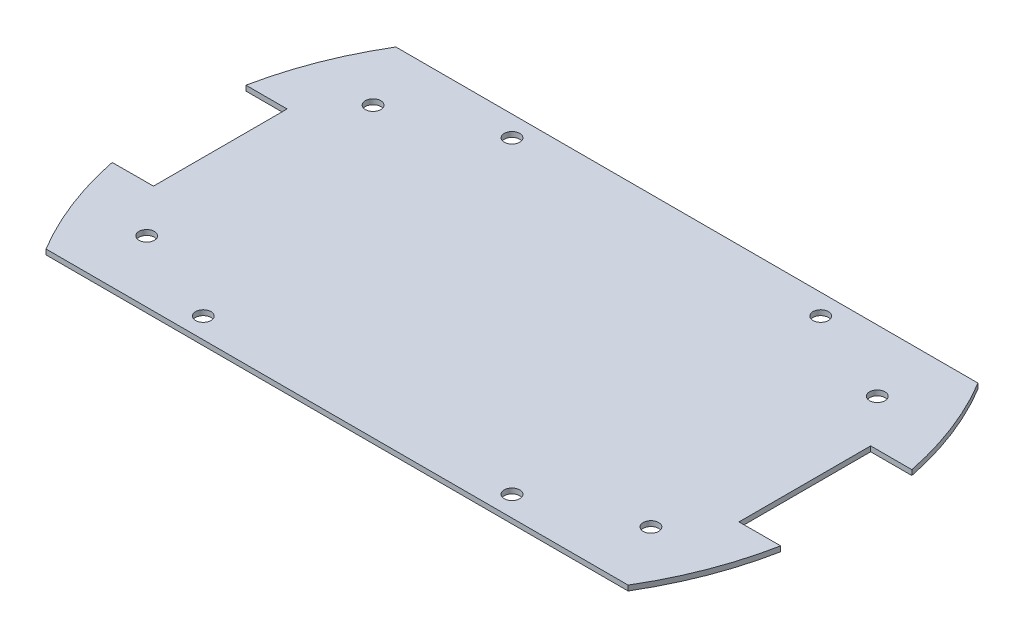
SolidWorks part; units mm, degrees
ref_plane "前基準面" through (0, 0, 0) normal (0, 0, 1) x (1, 0, 0)
ref_plane "上基準面" through (0, 0, 0) normal (0, 1, 0) x (1, 0, 0)
ref_plane "右基準面" through (0, 0, 0) normal (1, 0, 0) x (0, 0, -1)
sketch "草圖7" plane through (0, 0, 0) normal (0, 1, 0) x (1, 0, 0)
  line L1 (-34, 34) -> (34, 34)
  line L2 (-34, 34) -> (-34, -34)
  line L3 (-34, -34) -> (34, -34)
  line L4 (34, 34) -> (34, -34)
  line L5 (-34, 34) -> (34, -34) construction
  line L6 (-34, -34) -> (34, 34) construction
  point P0 (0, 0)
  point P7 (-30, 30)
  point P10 (30, 30)
  point P11 (30, -30)
  point P12 (-30, -30)
  point P13 (0, 0)
  dimension "D1" = 68
  dimension "D2" = 4
  dimension "D3" = 4
sketch "草圖10" plane through (0, 0, 0) normal (0, 1, 0) x (1, 0, 0)
  line L0 (-56.5685, 34) -> (56.5685, 34)
  line L1 (-34, 34) -> (34, 34) construction
  line L2 (-56.5685, -34) -> (56.5685, -34)
  line L3 (-34, -34) -> (34, -34) construction
  line L4 (-34, 34) -> (-34, -34) construction
  line L5 (0, 0) -> (0, 19.0172) construction
  line L6 (0, 0) -> (-12.2861, 0) construction
  line L7 (-56.707, 13) -> (-56.707, -13)
  line L8 (-64.707, 13) -> (64.707, 13)
  line L9 (56.707, 13) -> (56.707, -13)
  line L10 (-64.707, -13) -> (64.7924, -12.5675)
  arc A0 (-64.707, -13) -> (-56.5685, -34) centre (0, 0) ccw
  arc A3 (-56.5685, 34) -> (-64.707, 13) centre (0, 0) ccw
  arc A4 (64.707, 13) -> (56.5685, 34) centre (0, 0) ccw
  arc A5 (56.5685, -34) -> (64.7924, -12.5675) centre (0, 0) ccw
  point P4 (0, 0)
  point P5 (0, 0)
  point P8 (0, 0)
  point P9 (0, 0)
  point P12 (-49, 22)
  point P17 (0, 0)
  point P24 (56.707, 0)
  point P25 (0, 0)
  point P27 (-56.707, 0)
  point P28 (0, 0)
  dimension "D1" = 8
  dimension "D2" = 13
  dimension "D4" = 15
  dimension "D5" = 12
extrude "填料-伸長2" add sketch "草圖10" along normal blind 1 contours L7 L10 L9 L8 | L2 A5 L10 A0 | L8 A4 L0 A3 region at (0, 0, -23.2694) region at (-0.1389, 0, -0.1078) region at (0.2321, 0, 23.1574)
hole_wizard "Ø3.0mm 定位孔1" positions "3D草圖2" profile "草圖13" hole size "Ø3.0" standard "JIS"
sketch3d "3D草圖2"
  point P0 (-30, 0, -30)
  point P3 (-30, 1, -30)
  point P5 (-30, 1, 30)
  point P11 (30, 1, -30)
  point P13 (30, 1, 30)
  point P16 (0, 0, 0)
  point P17 (0, 0, 0)
  point P23 (0, 0, 0)
  point P24 (0, 0, 0)
  point P26 (0, 0, 0)
sketch "草圖13" plane through (30, 1, 30) normal (1, 0, 0) x (0, 0, 1)
  line L0 (0, 0) -> (0, 4.9013)
  line L1 (0, 4.9013) -> (1.5, 4)
  line L2 (1.5, 4) -> (1.5, 0)
  line L5 (1.5, 0) -> (0, 0)
  line L10 (0, 4.9013) -> (-1.5, 4) construction
  line L11 (0, -6.35) -> (0, 107.95) construction
  dimension "鑽孔直徑" = 3
  dimension "鑽孔深度" = 4
  dimension "導頭角度" = 118
hole_wizard "Ø3.0mm 定位孔2" positions "3D草圖3" profile "草圖14" hole size "Ø3.0" standard "JIS"
sketch3d "3D草圖3"
  point P0 (-49, 1, -22)
  point P3 (0, 0, 0)
  point P5 (0, 0, 0)
sketch "草圖14" plane through (-49, 1, -22) normal (1, 0, 0) x (0, 0, 1)
  line L0 (0, 0) -> (0, 4.9013)
  line L1 (0, 4.9013) -> (1.5, 4)
  line L2 (1.5, 4) -> (1.5, 0)
  line L5 (1.5, 0) -> (0, 0)
  line L10 (0, 4.9013) -> (-1.5, 4) construction
  line L11 (0, -6.35) -> (0, 107.95) construction
  dimension "鑽孔直徑" = 3
  dimension "鑽孔深度" = 4
  dimension "導頭角度" = 118
pattern_linear "直線複製排列1" count 2 spacing 98 along (1, 0, 0) count 2 spacing 44 along (0, 0, 1) of "Ø3.0mm 定位孔2"
